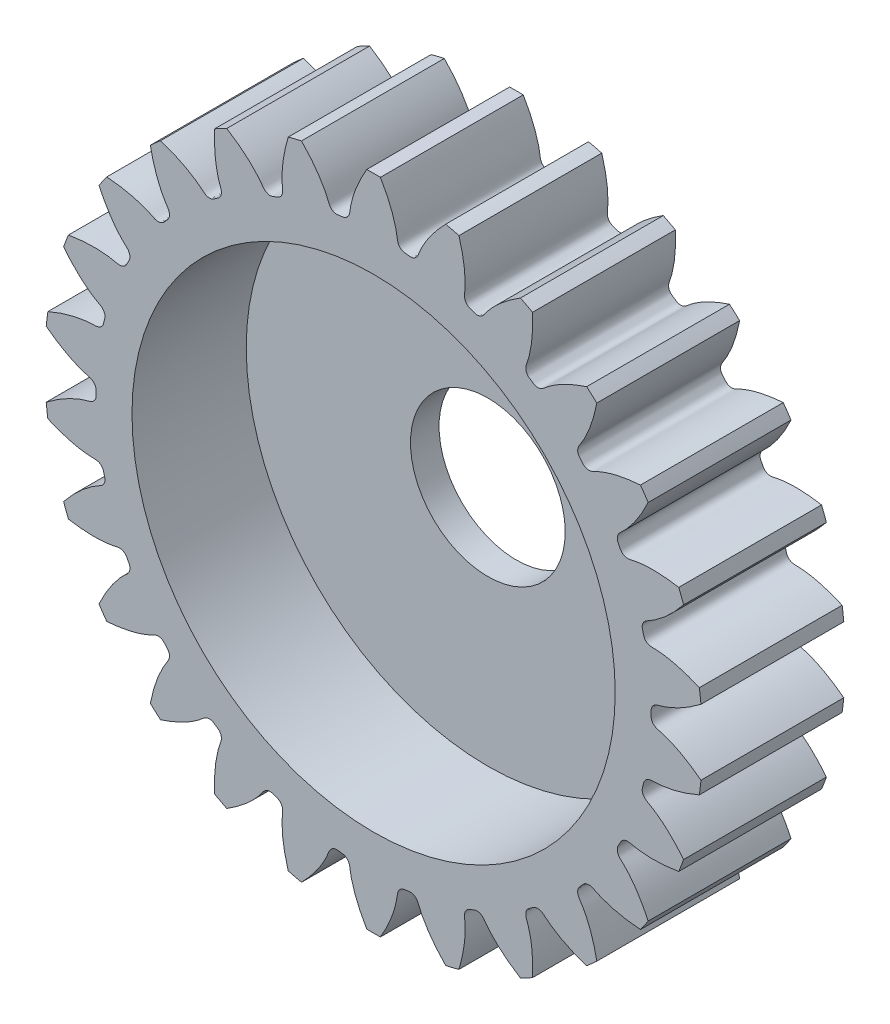
SolidWorks part; units mm, degrees
material "Д16 ГОСТ 4784-97"
ref_plane "FRONT" through (0, 0, 0) normal (0, 0, 1) x (1, 0, 0)
ref_plane "TOP" through (0, 0, 0) normal (0, 1, 0) x (1, 0, 0)
ref_plane "RIGHT" through (0, 0, 0) normal (1, 0, 0) x (0, 0, -1)
ref_axis "Ось1" through (0, 0, 50) along (0, 0, -1)
sketch "SketchRevolveSpurAssemblyNew2Pinion" plane through (0, 0, 0) normal (1, 0, 0) x (0, 0, -1)
  line L0 (0, 0) -> (1, 0) construction
  line L1 (-4, 0) -> (-4, 13.8221)
  line L2 (-4, 13.8221) -> (2, 13.8221)
  line L3 (2, 13.8221) -> (2, 0)
  line L4 (2, 0) -> (-4, 0)
  dimension "D1" = 4
  dimension "D2" = 6
revolve "SpurAssemblyNew2Pinion" add sketch "SketchRevolveSpurAssemblyNew2Pinion" angle 360 about L0
sketch "SketchToothSpurAssemblyNew2Pinion" plane through (0, 0, 0) normal (0, 0, 1) x (1, 0, 0)
  arc A0 (13.8145, 1.4289) -> (13.8145, -1.4289) centre (0, 0) cw
  spline S0 degree 3 poles (13.8145, -1.4289) (13.7267, -1.3599) (13.5952, -1.2613) (13.4189, -1.1388) (13.2926, -1.0553) (13.1699, -0.9783) (13.051, -0.9075) (12.9361, -0.8427) (12.8254, -0.7837) (12.7191, -0.7302) (12.6175, -0.6819) (12.5207, -0.6387) (12.4289, -0.6003) (12.3422, -0.5664) (12.2609, -0.5368) (12.185, -0.5112) (12.1147, -0.4893) (12.0271, -0.4637) (11.9541, -0.4482) (11.8978, -0.428) (11.8759, -0.419) (11.8534, -0.4085) (11.8302, -0.3959) (11.806, -0.3807) (11.7805, -0.3619) (11.7539, -0.3382) (11.7266, -0.3079) (11.7001, -0.2694) (11.6771, -0.2215) (11.6616, -0.1665) (11.6562, -0.0913) (11.6603, 0) (11.6562, 0.0913) (11.6616, 0.1665) (11.6771, 0.2215) (11.7001, 0.2694) (11.7266, 0.3079) (11.7539, 0.3382) (11.7805, 0.3619) (11.806, 0.3807) (11.8302, 0.3959) (11.8534, 0.4085) (11.8759, 0.419) (11.8978, 0.428) (11.9541, 0.4482) (12.0271, 0.4637) (12.1147, 0.4893) (12.185, 0.5112) (12.2609, 0.5368) (12.3422, 0.5664) (12.4289, 0.6003) (12.5207, 0.6387) (12.6175, 0.6819) (12.7191, 0.7302) (12.8254, 0.7837) (12.9361, 0.8427) (13.051, 0.9075) (13.1699, 0.9783) (13.2926, 1.0553) (13.4189, 1.1388) (13.5952, 1.2613) (13.7267, 1.3599) (13.8145, 1.4289) knots 0 0 0 0 0.061766 0.090857 0.118755 0.145459 0.170969 0.195285 0.218406 0.240334 0.261068 0.280608 0.298954 0.316106 0.332064 0.346827 0.360397 0.372773 0.397299 0.401522 0.405868 0.410405 0.415225 0.420444 0.426212 0.432709 0.440141 0.448702 0.45849 0.469388 0.4801 0.5 0.5199 0.530612 0.54151 0.551298 0.559859 0.567291 0.573788 0.579556 0.584775 0.589595 0.594132 0.598478 0.602701 0.627227 0.639603 0.653173 0.667936 0.683894 0.701046 0.719392 0.738932 0.759666 0.781594 0.804715 0.829031 0.854541 0.881245 0.909143 0.938234 1 1 1 1
extrude "ToothExtrudeCutSpurAssemblyNew2Pinion" cut sketch "SketchToothSpurAssemblyNew2Pinion" against normal blind 4 and the other way blind 4
pattern_circular "PatternSpurAssemblyNew2Pinion" count 26 every 13.846 about axis through (0, 0, 50) along (0, 0, -1) of "ToothExtrudeCutSpurAssemblyNew2Pinion"
sketch "AuxiliarySketchSpurAssemblyNew2Pinion" plane through (0, 0, 0) normal (0, 0, 1) x (1, 0, 0)
  circle A0 centre (0, 0) radius 12.5 construction
  circle A1 centre (0, 0) radius 11.7462 construction
  circle A2 centre (0, 0) radius 11.9829 construction
  circle A3 centre (0, 0) radius 13.8221 construction
  circle A4 centre (0, 0) radius 11.6587 construction
  dimension "PitchDiameter" = 25
  dimension "BaseDiameter" = 23.4923
  dimension "FormDiameter" = 23.9658
  dimension "MajorDiameter" = 27.6442
  dimension "MinorDiameter" = 23.3173
sketch "Эскиз3" plane through (0, 0, -2) normal (0, 0, -1) x (-1, 0, 0)
  circle A0 centre (0, 0) radius 9.5
sketch "Эскиз2" plane through (0, 0, 4) normal (0, 0, 1) x (1, 0, 0)
  circle A0 centre (0, 0) radius 10.15
extrude "Вырез-Вытянуть2" cut sketch "Эскиз2" against normal blind 4.8
sketch "Эскиз1" plane through (0, 0, -0.8) normal (0, 0, 1) x (1, 0, 0)
  circle A0 centre (0, 0) radius 7 construction
  circle A1 centre (0, 0) radius 8.25 construction
  circle A2 centre (0, 7) radius 1.25
  circle A3 centre (7, 0) radius 1.25
  circle A4 centre (0, -7) radius 1.25
  circle A5 centre (-7, 0) radius 1.25
  dimension "D1" = 14
  dimension "D2" = 16.5
sketch "Эскиз4" plane through (0, 0, -0.8) normal (0, 0, 1) x (1, 0, 0)
  circle A0 centre (0, 0) radius 3.25
  dimension "D1" = 6.5
extrude "Вырез-Вытянуть3" cut sketch "Эскиз4" against normal through all
